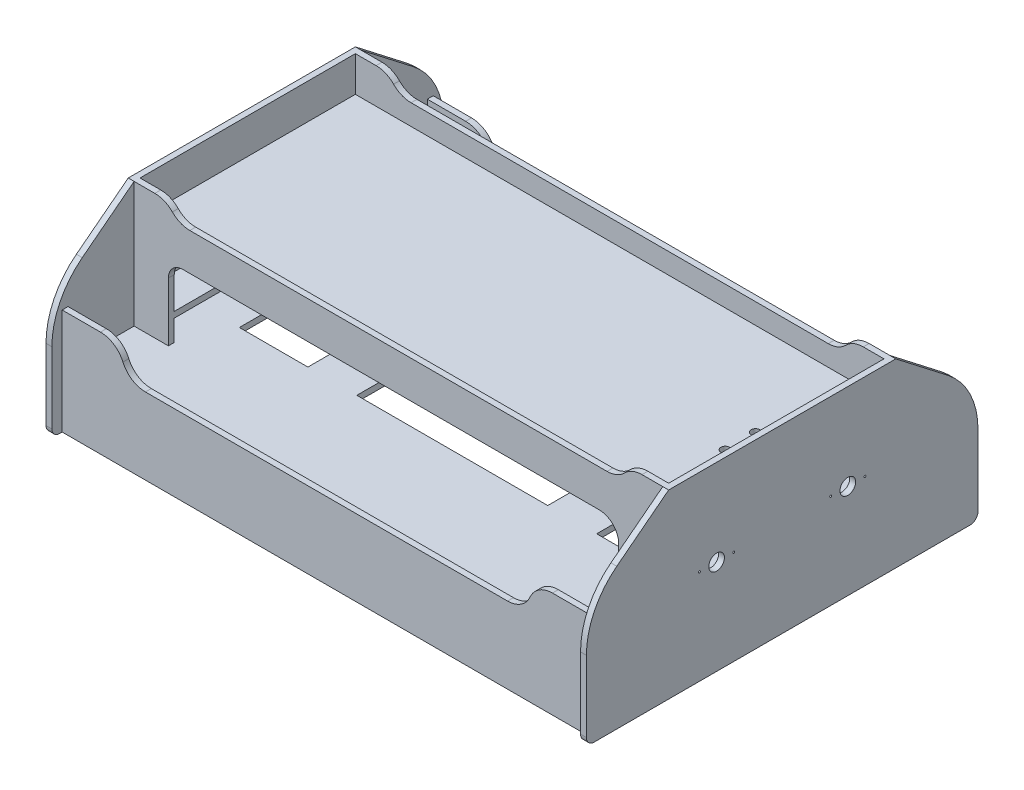
SolidWorks part; units mm, degrees
material "Birch plywood FK"
ref_plane "Спереди" through (0, 0, 0) normal (0, 0, 1) x (1, 0, 0)
ref_plane "Сверху" through (0, 0, 0) normal (0, 1, 0) x (1, 0, 0)
ref_plane "Справа" through (0, 0, 0) normal (1, 0, 0) x (0, 0, -1)
sketch "Эскиз2" plane through (0, 0, 0) normal (0, 1, 0) x (1, 0, 0)
  line L1 (216, -110) -> (-216, -110)
  line L2 (216, -110) -> (216, 110)
  line L3 (216, 110) -> (-216, 110)
  line L4 (-216, -110) -> (-216, 110)
  line L5 (216, -110) -> (-216, 110) construction
  line L6 (216, 110) -> (-216, -110) construction
  point P0 (0, 0)
  dimension "D1" = 220
  dimension "D2" = 432
extrude "Бобышка-Вытянуть2" add sketch "Эскиз2" along normal blind 6
sketch "Эскиз4" plane through (216, 0, 0) normal (1, 0, 0) x (0, 0, -1)
  line L0 (-110, 3) -> (110, 3) construction
  line L1 (-110, 6) -> (-110, 0) construction
  line L2 (110, 6) -> (110, 0) construction
  line L3 (-158, -13) -> (158, -13) construction
  line L4 (-110, -11) -> (-116, -11)
  line L5 (-110, -11) -> (-110, 17)
  line L6 (-110, 17) -> (-116, 17)
  line L7 (-116, -11) -> (-116, 17)
  line L8 (-110, -11) -> (-116, 17) construction
  line L9 (-110, 17) -> (-116, -11) construction
  line L10 (116, -11) -> (110, -11)
  line L11 (116, -11) -> (116, 17)
  line L12 (116, 17) -> (110, 17)
  line L13 (110, -11) -> (110, 17)
  line L14 (116, -11) -> (110, 17) construction
  line L15 (116, 17) -> (110, -11) construction
  point P6 (-113, 3)
  point P11 (113, 3)
  dimension "D1" = 2
extrude "Бобышка-Вытянуть3" add sketch "Эскиз4" against normal up to surface (432 mm away) up to face at (-216, 3, 0)
sketch "Эскиз5" plane through (-216, 0, 0) normal (-1, 0, 0) x (0, 0, 1)
  line L0 (-116, 17) -> (-110, 17)
  line L1 (-110, 17) -> (-110, 6)
  line L2 (-110, 6) -> (110, 6)
  line L3 (110, 6) -> (110, 17)
  line L4 (110, 17) -> (116, 17)
  line L5 (116, 17) -> (116, -11)
  line L6 (116, -11) -> (110, -11)
  line L7 (110, -11) -> (110, 0)
  line L8 (-110, 0) -> (110, 0) construction
  line L9 (110, 0) -> (110, -11) construction
  line L10 (110, 0) -> (-110, 0)
  line L11 (-110, 0) -> (-110, -11)
  line L12 (-110, -11) -> (-116, -11)
  line L13 (-116, -11) -> (-116, 17)
extrude "Бобышка-Вытянуть4" add sketch "Эскиз5" along normal blind 108
sketch "Эскиз6" plane through (0, 17, 0) normal (0, 1, 0) x (1, 0, 0)
  line L1 (216, -116) -> (-324, -116)
  line L2 (216, -116) -> (216, -110)
  line L3 (216, -110) -> (-324, -110)
  line L4 (-324, -116) -> (-324, -110)
  line L5 (216, 116) -> (-324, 116)
  line L6 (216, 116) -> (216, 110)
  line L7 (216, 110) -> (-324, 110)
  line L8 (-324, 116) -> (-324, 110)
extrude "Бобышка-Вытянуть5" add sketch "Эскиз6" along normal blind 25
sketch "Эскиз7" plane through (216, 0, 0) normal (1, 0, 0) x (0, 0, -1)
  line L0 (0, 0) -> (0, 6) construction
  line L1 (-110, 6) -> (110, 6) construction
  line L2 (-200, -143) -> (-200, -23)
  line L3 (-200, -23) -> (-116, 42)
  line L4 (-116, 42) -> (-110, 42) construction
  line L5 (-116, 42) -> (116, 42)
  line L6 (-200, -143) -> (200, -143)
  line L7 (200, -143) -> (200, -23)
  line L8 (200, -23) -> (116, 42)
  point P14 (0, -143)
  point P16 (0, 42)
  dimension "D1" = 120
  dimension "D2" = 200
  dimension "D3" = 185
extrude "Бобышка-Вытянуть6" add sketch "Эскиз7" along normal blind 6
sketch "Эскиз8" plane through (-324, 0, 0) normal (-1, 0, 0) x (0, 0, 1)
  line L0 (-116, 42) -> (-200, -23)
  line L1 (-200, -23) -> (-200, -143)
  line L2 (-200, -143) -> (200, -143)
  line L3 (200, -143) -> (200, -23)
  line L4 (200, -23) -> (116, 42)
  line L5 (116, 42) -> (-116, 42)
extrude "Бобышка-Вытянуть7" add sketch "Эскиз8" along normal blind 6
sketch "Эскиз9" plane through (-324, 0, 0) normal (1, 0, 0) x (0, 0, -1)
  line L0 (0, -83) -> (0, -143) construction
  line L1 (158, -83) -> (-158, -83) construction
  line L2 (-200, -143) -> (200, -143) construction
  line L4 (183.5, -92) -> (-183.5, -92)
  line L5 (183.5, -92) -> (183.5, -86)
  line L6 (183.5, -86) -> (-183.5, -86)
  line L7 (-183.5, -92) -> (-183.5, -86)
  line L8 (183.5, -92) -> (-183.5, -86) construction
  line L9 (183.5, -86) -> (-183.5, -92) construction
  point P6 (0, -89)
  dimension "D1" = 6
  dimension "D2" = 3
  dimension "D3" = 367
extrude "Бобышка-Вытянуть8" add sketch "Эскиз9" along normal up to surface (540 mm away) up to face at (216, -24.3333, 9.1667)
sketch "Эскиз10" plane through (-330, 0, 0) normal (-1, 0, 0) x (0, 0, 1)
  circle A0 centre (67, -46.2762) radius 8
  circle A1 centre (-67, -46.2762) radius 8
  dimension "D1" = 16
extrude "Вырез-Вытянуть1" cut sketch "Эскиз10" against normal through all
sketch "Эскиз11" plane through (222, 0, 0) normal (1, 0, 0) x (0, 0, -1)
  line L0 (-183.5, -89) -> (183.5, -89) construction
  line L1 (-183.5, -86) -> (-183.5, -92) construction
  line L2 (183.5, -92) -> (183.5, -86) construction
  line L3 (-200, -143) -> (200, -143) construction
  line L4 (189.5, -143) -> (183.5, -143)
  line L5 (189.5, -143) -> (189.5, -35)
  line L6 (189.5, -35) -> (183.5, -35)
  line L7 (183.5, -143) -> (183.5, -35)
  line L8 (189.5, -143) -> (183.5, -35) construction
  line L9 (189.5, -35) -> (183.5, -143) construction
  line L10 (-189.5, -143) -> (-183.5, -143)
  line L11 (-189.5, -143) -> (-189.5, -35)
  line L12 (-189.5, -35) -> (-183.5, -35)
  line L13 (-183.5, -143) -> (-183.5, -35)
  line L14 (-189.5, -143) -> (-183.5, -35) construction
  line L15 (-189.5, -35) -> (-183.5, -143) construction
  point P6 (186.5, -89)
  point P11 (-186.5, -89)
extrude "Бобышка-Вытянуть9" add sketch "Эскиз11" against normal up to surface (546 mm away) up to face at (-324, -46.2762, -59)
sketch "Эскиз12" plane through (0, -92, 0) normal (0, -1, 0) x (-1, 0, 0)
  line L0 (324, 0) -> (-216, 0) construction
  line L1 (324, 183.5) -> (324, -183.5) construction
  line L2 (-216, -183.5) -> (-216, 183.5) construction
  line L3 (324, -183.5) -> (-216, -183.5) construction
  line L4 (199, 63.5) -> (269, 63.5)
  line L5 (199, 63.5) -> (199, -63.5)
  line L6 (199, -63.5) -> (269, -63.5)
  line L7 (269, 63.5) -> (269, -63.5)
  line L8 (199, 63.5) -> (269, -63.5) construction
  line L9 (199, -63.5) -> (269, 63.5) construction
  line L10 (-46, 63.5) -> (149, 63.5)
  line L11 (-46, 63.5) -> (-46, -63.5)
  line L12 (-46, -63.5) -> (149, -63.5)
  line L13 (149, 63.5) -> (149, -63.5)
  line L14 (-46, 63.5) -> (149, -63.5) construction
  line L15 (-46, -63.5) -> (149, 63.5) construction
  line L16 (-166, 63.5) -> (-96, 63.5)
  line L17 (-166, 63.5) -> (-166, -63.5)
  line L18 (-166, -63.5) -> (-96, -63.5)
  line L19 (-96, 63.5) -> (-96, -63.5)
  line L20 (-166, 63.5) -> (-96, -63.5) construction
  line L21 (-166, -63.5) -> (-96, 63.5) construction
  point P6 (234, 0)
  point P11 (51.5, 0)
  point P16 (-131, 0)
  dimension "D1" = 55
  dimension "D2" = 50
  dimension "D3" = 50
  dimension "D4" = 50
  dimension "D5" = 120
  dimension "D6" = 195
extrude "Вырез-Вытянуть2" cut sketch "Эскиз12" against normal blind 6
sketch "Эскиз13" plane through (0, -86, 0) normal (0, 1, 0) x (1, 0, 0)
  line L0 (-227.5, 130) -> (-227.5, 114.6) construction
  line L1 (216, 110) -> (216, -110) construction
  line L2 (216, -21.15) -> (173.7, -21.15)
  line L3 (216, -21.15) -> (216, 21.15)
  line L4 (216, 21.15) -> (173.7, 21.15)
  line L5 (173.7, -21.15) -> (173.7, 21.15)
  line L6 (216, -21.15) -> (173.7, 21.15) construction
  line L7 (216, 21.15) -> (173.7, -21.15) construction
  line L8 (211.7574, 21.15) -> (177.9426, 21.15) construction
  circle A0 centre (-227.5, 122.3) radius 29
  point P7 (194.85, 0)
extrude "Вырез-Вытянуть3" cut sketch "Эскиз13" against normal blind 10
sketch "Эскиз14" plane through (216, 0, 0) normal (-1, 0, 0) x (0, 0, 1)
  line L0 (0, 42) -> (0, -143) construction
  line L1 (-116, 42) -> (116, 42) construction
  line L2 (200, -143) -> (-200, -143) construction
  line L4 (-110, -58.5) -> (110, -58.5)
  line L5 (-110, -58.5) -> (-110, -64.5)
  line L6 (-110, -64.5) -> (110, -64.5)
  line L7 (110, -58.5) -> (110, -64.5)
  line L8 (-110, -58.5) -> (110, -64.5) construction
  line L9 (-110, -64.5) -> (110, -58.5) construction
  line L10 (16.9074, -64.5) -> (-16.9074, -64.5) construction
  line L12 (110, 0) -> (110, -11) construction
  point P6 (0, -61.5)
  dimension "D1" = 6
extrude "Бобышка-Вытянуть10" add sketch "Эскиз14" along normal blind 45
sketch "Эскиз15" plane through (0, -58.5, 0) normal (0, 1, 0) x (1, 0, 0)
  circle A0 centre (194.85, 0) radius 16.4
  circle A1 centre (179.35, 15.5) radius 1.5
  circle A2 centre (210.35, 15.5) radius 1.5
  circle A3 centre (210.35, -15.5) radius 1.5
  circle A4 centre (179.35, -15.5) radius 1.5
  circle A5 centre (194.85, 0) radius 16.4 construction
  dimension "D1" = 3
extrude "Вырез-Вытянуть4" cut sketch "Эскиз15" against normal blind 6
sketch "Эскиз16" plane through (0, 6, 0) normal (0, 1, 0) x (1, 0, 0)
  circle A0 centre (179.35, 15.5) radius 4.5
  circle A1 centre (210.35, 15.5) radius 4.5
  circle A2 centre (179.35, -15.5) radius 4.5
  circle A3 centre (210.35, -15.5) radius 4.5
  dimension "D1" = 9
extrude "Вырез-Вытянуть5" cut sketch "Эскиз16" against normal blind 6
fillet "Скругление1" radius 80 4 edges at (-327, -23, -200) (219, -23, -200) (-327, -23, 200) (219, -23, 200)
fillet "Скругление2" radius 8 4 edges at (-327, -143, 200) (219, -143, 200) (-327, -143, -200) (219, -143, -200)
sketch "Эскиз18" plane through (216, 0, 0) normal (-1, 0, 0) x (0, 0, 1)
  line L1 (116, -11) -> (110, -11)
  line L2 (116, -11) -> (116, -86)
  line L3 (116, -86) -> (110, -86)
  line L4 (110, -11) -> (110, -86)
  line L5 (-183.5, -86) -> (183.5, -86) construction
  line L6 (-116, -11) -> (-110, -11)
  line L7 (-116, -11) -> (-116, -86)
  line L8 (-116, -86) -> (-110, -86)
  line L9 (-110, -11) -> (-110, -86)
extrude "Бобышка-Вытянуть11" add sketch "Эскиз18" along normal up to surface (45 mm away) up to face at (171, -61.5, 0)
sketch "Эскиз19" plane through (0, 0, 189.5) normal (0, 0, 1) x (1, 0, 0)
  line L0 (-264, -35) -> (-264, -65)
  line L1 (-324, -35) -> (216, -35) construction
  line L2 (-264, -65) -> (156, -65)
  line L3 (156, -65) -> (156, -35)
  line L4 (216, 1.0201) -> (216, -62.2496) construction
  line L5 (-324, -62.2496) -> (-324, 1.0201) construction
  line L6 (-324, 42) -> (216, 42) construction
  line L7 (-290, 42) -> (182, 42)
  line L8 (-290, 42) -> (-290, 27)
  line L9 (-290, 27) -> (182, 27)
  line L10 (182, 42) -> (182, 27)
  line L11 (-330, 1.0201) -> (-330, 42) construction
  line L12 (222, 42) -> (222, 1.0201) construction
  line L13 (-264, -35) -> (156, -35)
  dimension "D1" = 60
  dimension "D2" = 60
  dimension "D3" = 30
  dimension "D4" = 40
  dimension "D5" = 40
  dimension "D6" = 15
extrude "Вырез-Вытянуть8" cut sketch "Эскиз19" against normal through all
fillet "Скругление3" radius 25 8 edges at (-264, -65, 186.5) (156, -65, 186.5) (182, 27, 113) (-290, 27, 113) (-290, 27, -113) (182, 27, -113) (156, -65, -186.5) (-264, -65, -186.5)
fillet "Скругление4" radius 25 4 edges at (-264, -35, -186.5) (156, -35, -186.5) (156, -35, 186.5) (-264, -35, 186.5)
fillet "Скругление5" radius 25 4 edges at (-290, 42, -113) (-290, 42, 113) (182, 42, -113) (182, 42, 113)
fillet "Скругление6" radius 20 2 edges at (171, -11, 113) (171, -11, -113)
sketch "Эскиз20" plane through (-324, 0, 0) normal (1, 0, 0) x (0, 0, -1)
  line L1 (-116, -11) -> (-110, -11)
  line L2 (-116, -11) -> (-116, -86)
  line L3 (-116, -86) -> (-110, -86)
  line L4 (-110, -11) -> (-110, -86)
  line L5 (116, -11) -> (110, -11)
  line L6 (116, -11) -> (116, -86)
  line L7 (116, -86) -> (110, -86)
  line L8 (110, -11) -> (110, -86)
extrude "Бобышка-Вытянуть12" add sketch "Эскиз20" along normal blind 35
fillet "Скругление7" radius 15 2 edges at (-289, -11, -113) (-289, -11, 113)
sketch "Эскиз21" plane through (-324, 0, 0) normal (1, 0, 0) x (0, 0, -1)
  line L1 (110, -58.5) -> (-110, -58.5)
  line L2 (110, -58.5) -> (110, -64.5)
  line L3 (110, -64.5) -> (-110, -64.5)
  line L4 (-110, -58.5) -> (-110, -64.5)
extrude "Бобышка-Вытянуть13" add sketch "Эскиз21" along normal up to surface (35 mm away) up to face at (-289, -56, 113)
sketch "Эскиз22" plane through (222, 0, 0) normal (1, 0, 0) x (0, 0, -1)
  line L0 (-67, -46.2762) -> (-84.5, -46.2762) construction
  line L3 (-49.5, -46.2762) -> (-67, -46.2762) construction
  line L5 (49.5, -46.2762) -> (67, -46.2762) construction
  line L6 (67, -46.2762) -> (84.5, -46.2762) construction
  circle A0 centre (84.5, -46.2762) radius 1
  circle A1 centre (49.5, -46.2762) radius 1
  circle A2 centre (-49.5, -46.2762) radius 1
  circle A3 centre (-84.5, -46.2762) radius 1
  dimension "D1" = 2
  dimension "D2" = 17.5
extrude "Вырез-Вытянуть9" cut sketch "Эскиз22" against normal through all
sketch "Эскиз23" plane through (0, -86, 0) normal (0, 1, 0) x (1, 0, 0)
  line L0 (164.5142, -138.9) -> (154.5142, -138.9) construction
  line L1 (164.5142, -139.4) -> (154.5142, -139.4)
  line L2 (164.5142, -138.4) -> (154.5142, -138.4)
  line L3 (164.5142, -148.4) -> (154.5142, -148.4) construction
  line L4 (164.5142, -148.9) -> (154.5142, -148.9)
  line L5 (164.5142, -147.9) -> (154.5142, -147.9)
  arc A0 (164.5142, -139.4) -> (164.5142, -138.4) centre (164.5142, -138.9) ccw
  arc A1 (154.5142, -138.4) -> (154.5142, -139.4) centre (154.5142, -138.9) ccw
  arc A2 (164.5142, -148.9) -> (164.5142, -147.9) centre (164.5142, -148.4) ccw
  arc A3 (154.5142, -147.9) -> (154.5142, -148.9) centre (154.5142, -148.4) ccw
  point P2 (159.5142, -138.9)
  point P7 (159.5142, -148.4)
  dimension "D1" = 1
  dimension "D2" = 10
extrude "Вырез-Вытянуть10" cut sketch "Эскиз23" against normal through all
